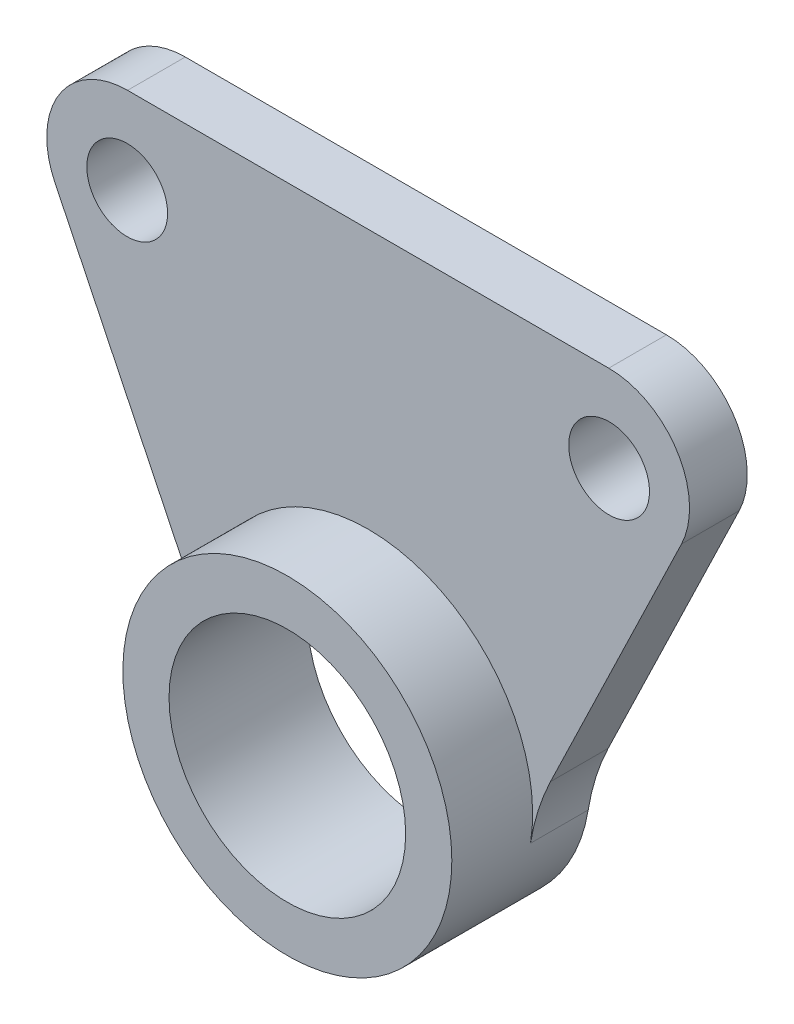
SolidWorks part; units mm, degrees
ref_plane "Plan de face" through (0, 0, 0) normal (0, 0, 1) x (1, 0, 0)
ref_plane "Plan de dessus" through (0, 0, 0) normal (0, 1, 0) x (1, 0, 0)
ref_plane "Plan de droite" through (0, 0, 0) normal (1, 0, 0) x (0, 0, -1)
sketch "Esquisse1" plane through (0, 0, 0) normal (0, 0, 1) x (1, 0, 0)
  line L0 (-7.125, 0) -> (-15.9984, 18.375)
  line L1 (15.9984, 18.375) -> (-15.9984, 18.375)
  line L2 (7.125, 0) -> (15.9984, 18.375)
  line L3 (0, 0) -> (0, 18.375) construction
  line L4 (-10.4375, 14.625) -> (10.4375, 14.625) construction
  line L5 (-10.4375, 14.625) -> (-14.1875, 14.625) construction
  line L6 (-10.4375, 14.625) -> (-10.4375, 18.375) construction
  line L7 (0, 0) -> (0, 9.625) construction
  circle A0 centre (0, 0) radius 5.125
  circle A1 centre (0, 0) radius 7.125
  circle A4 centre (-10.4375, 14.625) radius 1.75
  circle A5 centre (10.4375, 14.625) radius 1.75
  point P13 (0, 14.625)
  dimension "D1" = 10.25
  dimension "D4" = 20.875
  dimension "D5" = 3.5
  dimension "D3" = 14.625
  dimension "D6" = 3.75
  dimension "D7" = 9.625
  dimension "D2" = 2
extrude "Boss.-Extru.1" add sketch "Esquisse1" along normal blind 6 contours A0 A1 region at (0, 6.9235, 0)
extrude "Boss.-Extru.2" add sketch "Esquisse1<3>" along normal blind 2.5 contours A1 L3 L1 | L3 A1 L1 region at (0, 11.9067, 0)
sketch "Esquisse1<3>" plane through (0, 0, 0) normal (0, 0, 1) x (1, 0, 0) same geometry as "Esquisse1"
fillet "Congé1" radius 3.5 2 edges at (15.9984, 18.375, 1.25) (-15.9984, 18.375, 1.25)
fillet "Congé2" radius 10 2 edges at (-7.125, 0, 1.25) (7.125, 0, 1.25)
